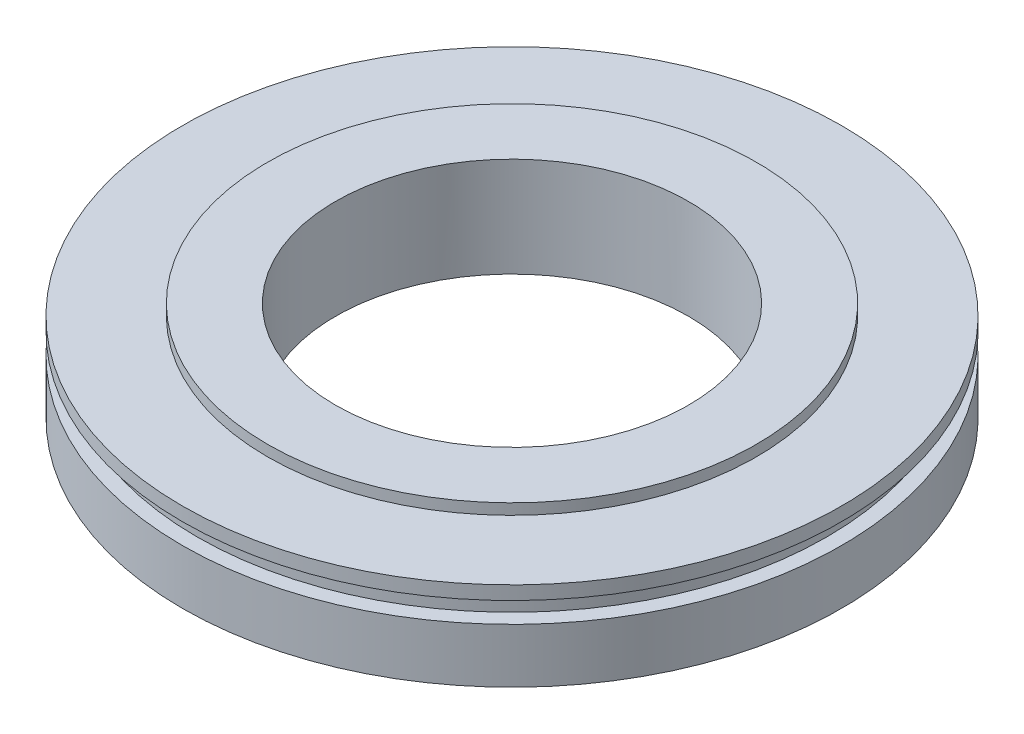
SolidWorks part; units mm, degrees
material "6061-T6 (SS)"
ref_plane "X-Y Datum" through (0, 0, 0) normal (0, 0, 1) x (1, 0, 0)
ref_plane "X-Z Datum" through (0, 0, 0) normal (0, 1, 0) x (1, 0, 0)
ref_plane "Y-Z Datum" through (0, 0, 0) normal (1, 0, 0) x (0, 0, -1)
sketch "Sketch1" plane through (0, 0, 0) normal (1, 0, 0) x (0, 0, -1)
  line L0 (-16.51, 2.6941) -> (-16.51, -5.0208)
  line L1 (-16.51, -5.0208) -> (-30.8229, -5.0208)
  line L4 (-29.4386, -0.5063) -> (-29.4386, 1.4241)
  line L7 (-30.8229, 2.6941) -> (-16.51, 2.6941)
  line L8 (0, 0) -> (0, -47872.0541) construction
  line L9 (0, 0) -> (-47872.0541, 0) construction
  line L10 (-30.8229, -0.5063) -> (-30.8229, -5.0208)
  line L11 (-14.7421, 2.6941) -> (15.0495, 2.6941) construction
  line L12 (-30.9994, 12.7) -> (-30.9994, -12.7) construction
  line L13 (14.2875, -5.0208) -> (-14.2875, -5.0208) construction
  line L15 (-30.8229, 2.6941) -> (-30.8229, 1.4241)
  line L16 (-30.8229, 1.4241) -> (-29.4386, 1.4241)
  line L17 (-29.4386, -0.5063) -> (-30.8229, -0.5063)
  point P15 (-30.9994, 0)
  dimension "D3" = 1.27
  dimension "D1" = 33.02
  dimension "D2" = 61.6458
  dimension "D4" = 1.9304
  dimension "D5" = 25.4
  dimension "D6" = 61.9989
  dimension "D7" = 58.8772
revolve "Revolve1" add sketch "Sketch1" angle 360 about L8
ref_plane "Plane1" through (0, 1.4241, 0) normal (0, 1, 0) x (1, 0, 0)
sketch "Sketch3" plane through (0, 2.6941, 0) normal (0, 1, 0) x (1, 0, 0)
  circle A0 centre (0, 0) radius 30.8229
  circle A1 centre (0, 0) radius 16.51
  circle A2 centre (0, 0) radius 16.51 construction
  circle A4 centre (0, 0) radius 30.8229 construction
extrude "BandAid Solution thicker" add sketch "Sketch3" along normal up to surface (-1.27 mm away) up to plane "Plane1"
sketch "Sketch4" plane through (0, 2.6941, 0) normal (0, 1, 0) x (1, 0, 0)
  circle A0 centre (0, 0) radius 16.51
  circle A1 centre (0, 0) radius 22.86
  circle A3 centre (0, 0) radius 16.51 construction
  dimension "D1" = 45.72
extrude "Lip for Bearing" add sketch "Sketch4" along normal blind 1.016
sketch "Sketch5" plane through (0, -5.0208, 0) normal (0, -1, 0) x (1, 0, 0)
  circle A3 centre (0, 0) radius 16.51
  circle A4 centre (0, 0) radius 30.8229
  circle A5 centre (0, 0) radius 30.8229 construction
  circle A6 centre (0, 0) radius 16.51 construction
extrude "Boss-Extrude1" add sketch "Sketch5" along normal blind 0.5791
move or copy body "Body-Move/Copy1" [suppressed] bodies to move or copy 105 parameters "D1"=0, "D2"=0, "D3"=0
